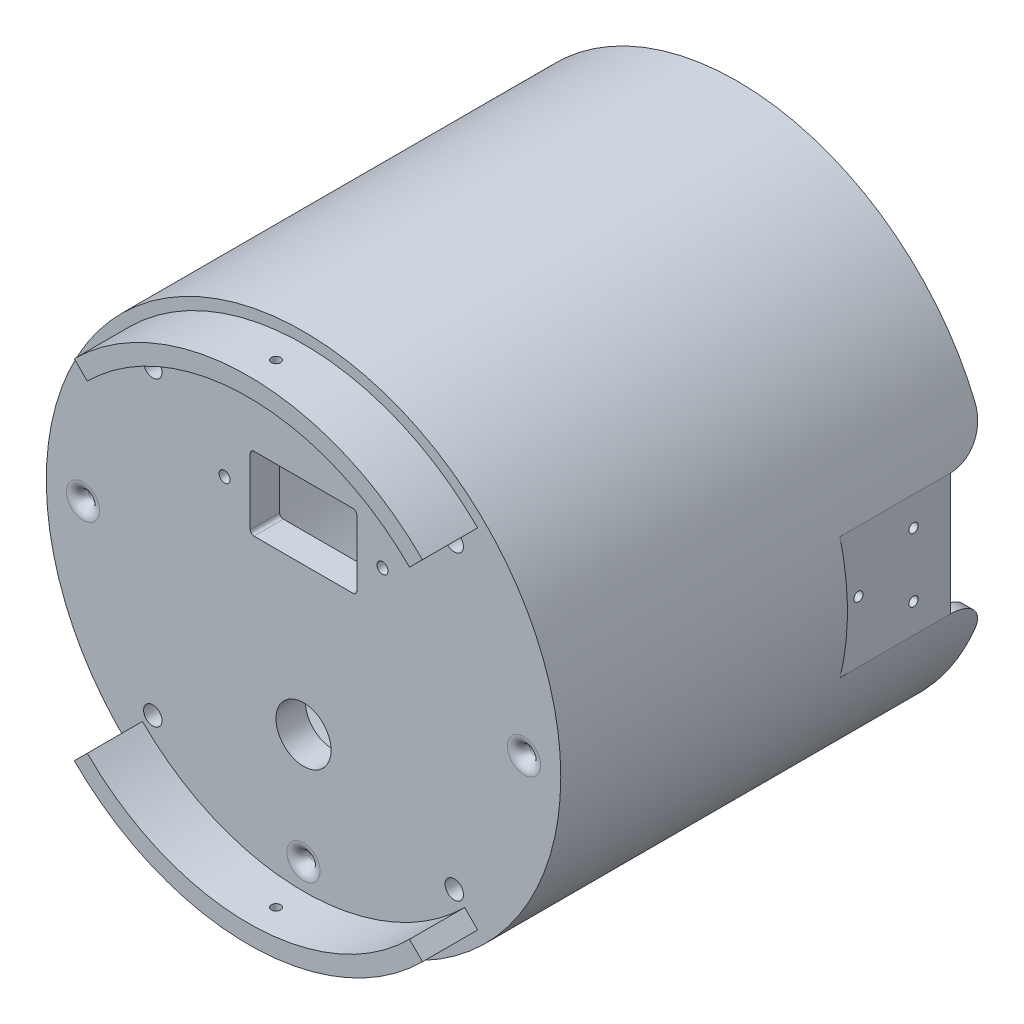
SolidWorks part; units mm, degrees
ref_plane "Front Plane" through (0, 0, 0) normal (0, 0, 1) x (1, 0, 0)
ref_plane "Top Plane" through (0, 0, 0) normal (0, 1, 0) x (1, 0, 0)
ref_plane "Right Plane" through (0, 0, 0) normal (1, 0, 0) x (0, 0, -1)
sketch "Sketch1" plane through (0, 0, 0) normal (0, 0, 1) x (1, 0, 0)
  circle A0 centre (0, 0) radius 70
  circle A1 centre (0, 0) radius 67
  dimension "D1" = 140
  dimension "D2" = 134
extrude "Boss-Extrude1" add sketch "Sketch1" along normal blind 8 contours A1 | A0 A1 region at (-68.0201, 0, 0) region at (0, 0, 0)
sketch "Sketch2" plane through (0, 0, 8) normal (0, 0, 1) x (1, 0, 0)
  circle A0 centre (-60, 0) radius 1.5
  circle A2 centre (60, 0) radius 1.5
  circle A4 centre (0, 60) radius 1.5 [skipped]
  circle A5 centre (0, -60) radius 1.5 [skipped]
  circle A6 centre (0, 55) radius 1.5
  circle A7 centre (0, -55) radius 1.5
  point P11 (0, 0)
  point P12 (0, 0)
  point P13 (0, 0)
  dimension "D1" = 3
  dimension "D4" = 3
  dimension "D2" = 60
  dimension "D5" = 55
  dimension "D3" = 4
  dimension "D6" = 2
extrude "Cut-Extrude2" cut sketch "Sketch2" against normal blind 20
extrude "Boss-Extrude2" add sketch "Sketch1<3>" against normal blind 100
sketch "Sketch1<3>" plane through (0, 0, 0) normal (0, 0, 1) x (1, 0, 0) same geometry as "Sketch1"
sketch "Sketch3" plane through (0, 0, 8) normal (0, 0, 1) x (1, 0, 0)
  line L0 (43.8406, -43.8406) -> (47.3762, -47.3762)
  line L2 (47.3762, 47.3762) -> (43.8406, 43.8406)
  line L4 (-43.8406, 43.8406) -> (-47.3762, 47.3762)
  line L6 (-43.8406, -43.8406) -> (-47.3762, -47.3762)
  arc A0 (-47.3762, -47.3762) -> (47.3762, -47.3762) centre (0, 0) ccw
  arc A1 (-43.8406, -43.8406) -> (43.8406, -43.8406) centre (0, 0) ccw
  arc A2 (43.8406, 43.8406) -> (-43.8406, 43.8406) centre (0, 0) ccw
  arc A3 (47.3762, 47.3762) -> (-47.3762, 47.3762) centre (0, 0) ccw
  dimension "D1" = 5
extrude "Boss-Extrude3" add sketch "Sketch3" along normal blind 15 contours A1 L6 A0 L0 | A2 L4 A3 L2 region at (44.9187, -46.2981, 8)
sketch "Sketch5" plane through (0, 0, 0) normal (0, 1, 0) x (1, 0, 0)
  line L0 (-47.3762, -23) -> (47.3762, -23) construction
  circle A0 centre (0, -15.5) radius 1.25
  dimension "D2" = 2.5
  dimension "D1" = 7.5
extrude "Cut-Extrude3" cut sketch "Sketch5" against normal blind 117 and the other way blind 117 contours A0
sketch "Sketch7" plane through (0, 0, 8) normal (0, 0, 1) x (1, 0, 0)
  circle A4 centre (41.0122, 41.0122) radius 2.5
  circle A5 centre (41.0122, -41.0122) radius 2.5
  circle A6 centre (-41.0122, -41.0122) radius 2.5
  circle A7 centre (-41.0122, 41.0122) radius 2.5
  point P11 (0, 0)
  point P12 (0, 0)
  dimension "D1" = 5
  dimension "D2" = 4
  dimension "D3" = 58
fillet "Fillet4" radius 3 4 edges at (61.5, 0, 8) (1.5, -55, 8) (-58.5, 0, 8) (1.5, 55, 8)
sketch "Sketch10" plane through (0, 0, 8) normal (0, 0, 1) x (1, 0, 0)
  line L0 (0, 55) -> (0, -55) construction
  line L1 (-43.1838, 5.5) -> (-33.1838, 5.5)
  line L2 (-43.1838, 5.5) -> (-43.1838, -5.5)
  line L3 (-43.1838, -5.5) -> (-33.1838, -5.5)
  line L4 (-33.1838, 5.5) -> (-33.1838, -5.5)
  line L5 (-43.1838, 5.5) -> (-33.1838, -5.5) construction
  line L6 (-43.1838, -5.5) -> (-33.1838, 5.5) construction
  line L7 (43.1838, -5.5) -> (33.1838, 5.5) construction
  line L8 (43.1838, 5.5) -> (33.1838, -5.5) construction
  line L9 (33.1838, 5.5) -> (33.1838, -5.5)
  line L10 (43.1838, -5.5) -> (33.1838, -5.5)
  line L11 (43.1838, 5.5) -> (43.1838, -5.5)
  line L12 (43.1838, 5.5) -> (33.1838, 5.5)
  point P0 (-38.1838, 0)
  point P11 (38.1838, 0)
  dimension "D1" = 10
  dimension "D2" = 11
extrude "Cut-Extrude6" cut sketch "Sketch7" against normal blind 14
sketch "Sketch8" plane through (0, 0, 0) normal (0, 0, -1) x (-1, 0, 0)
  line L0 (39.8411, 36.6638) -> (44.1925, 37.8238)
  line L1 (-36.6638, 39.8411) -> (-37.8238, 44.1925)
  line L2 (-37.8238, 44.1925) -> (-42.1722, 45.3635)
  line L3 (-42.1722, 45.3635) -> (-45.3606, 42.1832)
  line L4 (-45.3606, 42.1832) -> (-44.2006, 37.8319)
  line L5 (-44.2006, 37.8319) -> (-39.8521, 36.6608)
  line L6 (-39.8521, 36.6608) -> (-36.6638, 39.8411)
  line L7 (44.1925, 37.8238) -> (45.3635, 42.1722)
  line L8 (45.3635, 42.1722) -> (42.1832, 45.3606)
  line L9 (42.1832, 45.3606) -> (37.8319, 44.2006)
  line L10 (37.8319, 44.2006) -> (36.6608, 39.8521)
  line L11 (36.6608, 39.8521) -> (39.8411, 36.6638)
  line L12 (36.6638, -39.8411) -> (37.8238, -44.1925)
  line L13 (37.8238, -44.1925) -> (42.1722, -45.3635)
  line L14 (42.1722, -45.3635) -> (45.3606, -42.1832)
  line L15 (45.3606, -42.1832) -> (44.2006, -37.8319)
  line L16 (44.2006, -37.8319) -> (39.8521, -36.6608)
  line L17 (39.8521, -36.6608) -> (36.6638, -39.8411)
  line L18 (-39.8411, -36.6638) -> (-44.1925, -37.8238)
  line L19 (-44.1925, -37.8238) -> (-45.3635, -42.1722)
  line L20 (-45.3635, -42.1722) -> (-42.1832, -45.3606)
  line L21 (-42.1832, -45.3606) -> (-37.8319, -44.2006)
  line L22 (-37.8319, -44.2006) -> (-36.6608, -39.8521)
  line L23 (-36.6608, -39.8521) -> (-39.8411, -36.6638)
  circle A0 centre (-41.0122, 41.0122) radius 3.9 construction
  circle A1 centre (41.0122, 41.0122) radius 3.9 construction
  circle A2 centre (41.0122, -41.0122) radius 3.9 construction
  circle A3 centre (-41.0122, -41.0122) radius 3.9 construction
  point P1 (-38.258, 38.251)
  point P37 (0, 0)
  dimension "D1" = 7.8
  dimension "D2" = 4
extrude "Cut-Extrude7" cut sketch "Sketch8" against normal blind 2
sketch "Sketch9" plane through (0, 0, 8) normal (0, 0, 1) x (1, 0, 0)
  line L0 (0, 55) -> (0, -55) construction
  line L1 (14.5, 15) -> (14.5, 35)
  line L2 (14.5, 15) -> (-14.5, 15)
  line L3 (-14.5, 15) -> (-14.5, 35)
  line L4 (14.5, 35) -> (-14.5, 35)
  line L5 (14.5, 15) -> (-14.5, 35) construction
  line L6 (-14.5, 15) -> (14.5, 35) construction
  circle A0 centre (-21.5, 25) radius 1.5
  circle A1 centre (21.5, 25) radius 1.5
  circle A2 centre (0, -25) radius 7.5
  point P0 (0, 25)
  dimension "D3" = 3
  dimension "D5" = 3
  dimension "D7" = 25
  dimension "D1" = 20
  dimension "D2" = 29
  dimension "D4" = 7
  dimension "D6" = 7
extrude "Cut-Extrude8" cut sketch "Sketch9" against normal blind 28
sketch "Sketch11" plane through (0, 0, -100) normal (0, 0, -1) x (-1, 0, 0)
  line L0 (65.5, 24.6931) -> (65.5, -24.6931)
  line L1 (65.5, -24.6931) -> (65.5, 0)
  line L2 (65.5, 0) -> (70, 0)
  arc A0 (65.5, -24.6931) -> (65.5, 24.6931) centre (0, 0) ccw
  circle M3 centre (0, 0) radius 67
  circle M4 centre (0, 0) radius 70
  dimension "D1" = 4.5
extrude "Boss-Extrude4" add sketch "Sketch11" against normal blind 30 contours L0 L2 M3 | L2 L0 M3 | L2 L0 M3 M4 | L2 L0 M3 M4 region at (-67.5866, 10.2375, -100) region at (-66.1006, 5.2947, -100) region at (-67.5866, -10.2375, -100) region at (-66.1006, -5.2947, -100)
sketch "Sketch13" plane through (-65.5, 0, 0) normal (1, 0, 0) x (0, 0, -1)
  line L0 (70, 0) -> (76.25, 0) construction
  line L1 (70, 14.0979) -> (70, -14.0979) construction
  line L2 (100, 14.0979) -> (100, -14.0979) construction
  line L3 (85, 14.0979) -> (85, 10) construction
  line L4 (70, 14.0979) -> (100, 14.0979) construction
  line L5 (100, -14.0979) -> (70, -14.0979) construction
  line L6 (85, -10) -> (85, -14.0979) construction
  line L7 (95, 0) -> (100, 0) construction
  arc A0 (75.0781, 1.2476) -> (75.0781, -1.2476) centre (85, 0) ccw
  circle A1 centre (75, 0) radius 1.25
  circle A2 centre (90, 8.6603) radius 1.25
  circle A3 centre (90, -8.6603) radius 1.25
  arc A4 (91.0414, 7.9688) -> (88.8805, 9.2164) centre (85, 0) ccw
  arc A5 (88.8805, -9.2164) -> (91.0414, -7.9688) centre (85, 0) ccw
  dimension "D1" = 120
  dimension "D2" = 120
extrude "Cut-Extrude9" cut sketch "Sketch13" against normal blind 40 contours A4 A2 | A2 A4 | A0 A1 | A0 A1 | A3 A5 | A5 A3 region at (-65.5, 0, -75.5443) region at (-65.5, 0, -74.4838) region at (-65.5, 9.1073, -90.2581) region at (-65.5, 8.1888, -89.7278) region at (-65.5, -9.1073, -90.2581) region at (-65.5, -8.1888, -89.7278)
mirror "Mirror2" about plane through (0, 0, 0) normal (1, 0, 0) of "Cut-Extrude9", "Boss-Extrude4"
fillet "Fillet5" radius 1 4 edges at (-14.5, 35, 4) (-14.5, 15, 4) (14.5, 15, 4) (14.5, 35, 4)
sketch "Sketch14" plane through (0, 0, -100) normal (0, 0, -1) x (-1, 0, 0)
  line L0 (68, 16.6132) -> (68, -16.6132)
  line L1 (68, 0) -> (70, 0)
  circle A0 centre (0, 0) radius 70
  circle M7 centre (0, 0) radius 70
  dimension "D1" = 2
extrude "Cut-Extrude10" cut sketch "Sketch14" against normal blind 30 contours L0 L1 M7 | L1 L0 M7 region at (-68.801, 6.242, -100) region at (-68.801, -6.242, -100)
mirror "Mirror4" about plane through (0, 0, 0) normal (1, 0, 0) of "Cut-Extrude10"
sketch "Sketch15" plane through (0, 0, -100) normal (0, 0, -1) x (-1, 0, 0)
  line L3 (-68, -16.6132) -> (-64.9076, -16.6132)
  line L4 (-68, 16.6132) -> (-64.9076, 16.6132)
  line L5 (68, 16.6132) -> (64.9076, 16.6132)
  line L6 (68, -16.6132) -> (64.9076, -16.6132)
  arc A2 (-64.9076, -16.6132) -> (64.9076, -16.6132) centre (0, 0) ccw
  arc A3 (-68, -16.6132) -> (68, -16.6132) centre (0, 0) ccw
  arc A4 (64.9076, 16.6132) -> (-64.9076, 16.6132) centre (0, 0) ccw
  arc A5 (68, 16.6132) -> (-68, 16.6132) centre (0, 0) ccw
  point P4 (0, 0)
extrude "Boss-Extrude5" add sketch "Sketch15" along normal blind 10 contours A4 L4 A5 L5 | A3 L6 A2 L3
fillet "Fillet6" radius 10 4 edges at (-66.4538, -16.6132, -110) (-66.4538, 16.6132, -110) (66.4538, -16.6132, -110) (66.4538, 16.6132, -110)
